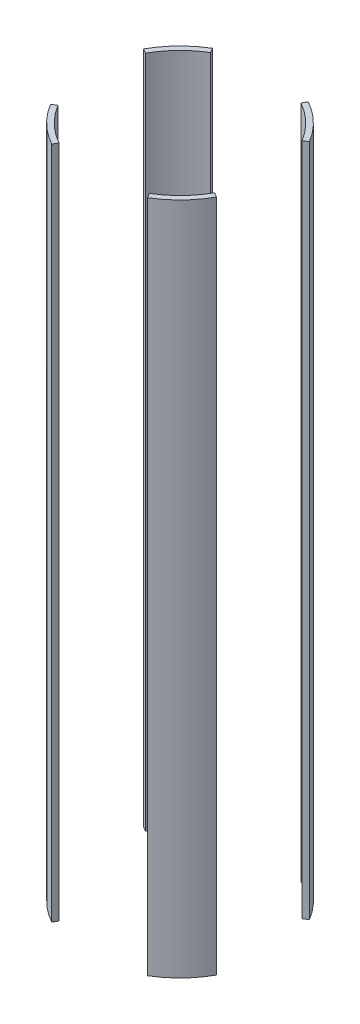
SolidWorks part; units mm, degrees
ref_plane "Front Plane" through (0, 0, 0) normal (0, 0, 1) x (1, 0, 0)
ref_plane "Top Plane" through (0, 0, 0) normal (0, 1, 0) x (1, 0, 0)
ref_plane "Right Plane" through (0, 0, 0) normal (1, 0, 0) x (0, 0, -1)
sketch "Sketch2" plane through (0, 0, 0) normal (0, 1, 0) x (1, 0, 0)
  circle A0 centre (0, 0) radius 88.9
  circle A1 centre (0, 0) radius 83.82
  dimension "D1" = 177.8
  dimension "D2" = 167.64
extrude "Boss-Extrude1" add sketch "Sketch2" along normal mid plane 635
sketch "Sketch3" plane through (0, 0, 0) normal (0, 1, 0) x (1, 0, 0)
  line L0 (0, 0) -> (169.6618, 101.6776)
  line L1 (-58.1167, 96.9749) -> (0, 0)
  line L2 (0, 0) -> (53.9, 96.9749)
  line L3 (53.9, 96.9749) -> (-58.1167, 96.9749)
  line L4 (0, 0) -> (70.9917, -118.4586)
  line L5 (70.9917, -118.4586) -> (-65.8409, -118.4586)
  line L6 (-65.8409, -118.4586) -> (0, 0)
  line L7 (169.6618, 101.6776) -> (169.6618, -94.3004)
  line L8 (169.6618, -94.3004) -> (0, 0)
  line L9 (0, 0) -> (-123.7413, 68.7771)
  line L10 (-123.7413, 68.7771) -> (-123.7413, -74.1577)
  line L11 (-123.7413, -74.1577) -> (0, 0)
  dimension "D1" = 60
  dimension "D2" = 60
  dimension "D3" = 60
  dimension "D4" = 60
  dimension "D5" = 30
  dimension "D6" = 30
extrude "Cut-Extrude1" cut sketch "Sketch3" against normal through all both and the other way through all contours L8 L7 L0 | L2 L3 L1 | L10 L11 L9 | L6 L5 L4 region at (-1.4056, 0, -64.65) region at (1.7169, 0, 78.9724) region at (113.1078, 0, -2.4591) region at (-82.4942, 0, 1.7935)
sketch "Sketch4" plane through (0, -317.5, 0) normal (0, -1, 0) x (1, 0, 0)
  circle A0 centre (0, 0) radius 88.9
  circle A1 centre (0, 0) radius 76.2
  dimension "D1" = 152.4
  dimension "D2" = 177.8
extrude "Boss-Extrude2" [suppressed] add sketch "Sketch4" against normal blind 12.7
equation "\"D1@Boss-Extrude1\"=3*12"
